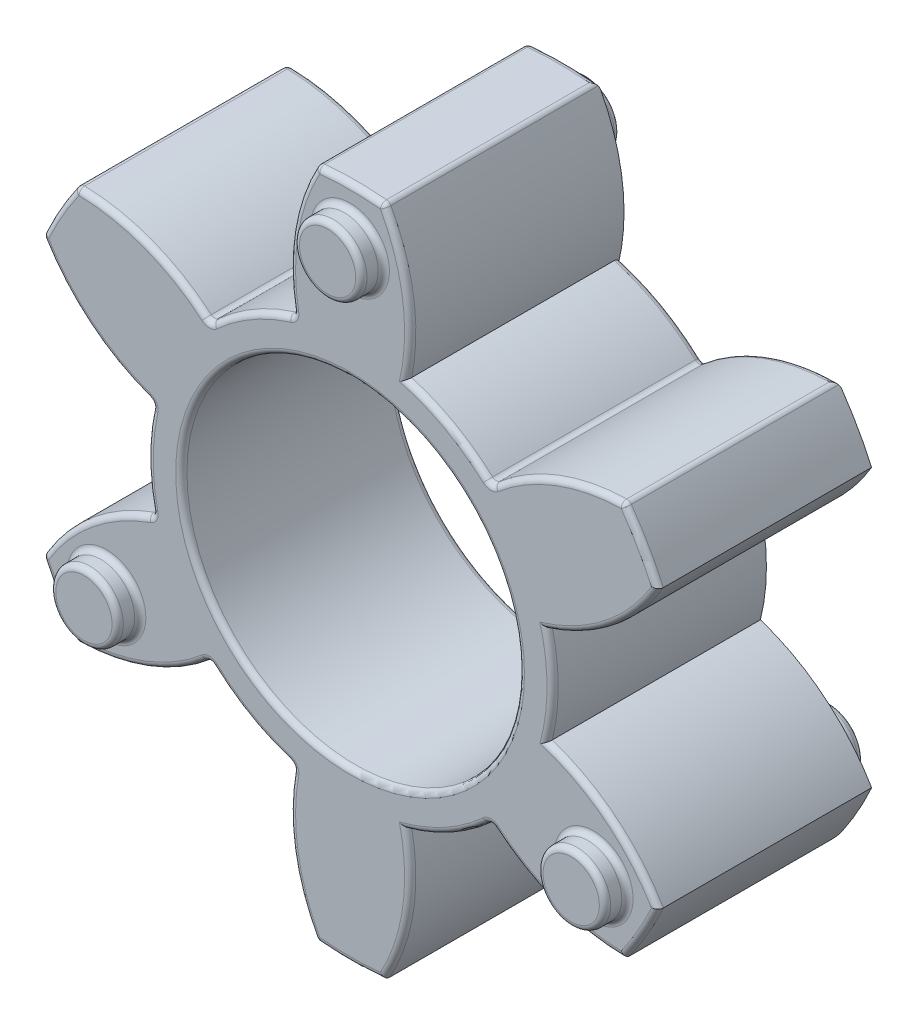
SolidWorks part; units mm, degrees
ref_plane "Front Plane" through (0, 0, 0) normal (0, 0, 1) x (1, 0, 0)
ref_plane "Top Plane" through (0, 0, 0) normal (0, 1, 0) x (1, 0, 0)
ref_plane "Right Plane" through (0, 0, 0) normal (1, 0, 0) x (0, 0, -1)
sketch "Sketch1" plane through (0, 0, 0) normal (0, 0, 1) x (1, 0, 0)
  line L0 (0, 0) -> (0, 50000) construction
  line L1 (0, 0) -> (-50000, 0) construction
  circle A0 centre (0, 0) radius 7.5
  circle A1 centre (0, 0) radius 12.5 construction
  arc A2 (-8.7337, 2.173) -> (-8.7337, -2.173) centre (0, 0) ccw
  circle A3 centre (0, 12.5) radius 1.5
  arc A4 (-12.1753, 8.7614) -> (-13.6753, 6.1634) centre (0, 0) ccw
  arc A5 (-2.485, 8.6501) -> (-1.5, 14.9248) centre (6.3267, 10.4815) cw
  arc A6 (2.485, 8.6501) -> (1.5, 14.9248) centre (-6.3267, 10.4815) ccw
  arc A7 (6.2487, 6.4771) -> (12.1753, 8.7614) centre (12.2406, -0.2383) cw
  arc A8 (8.7337, 2.173) -> (13.6753, 6.1634) centre (5.9139, 10.7198) ccw
  arc A10 (8.7337, -2.173) -> (13.6753, -6.1634) centre (5.9139, -10.7198) cw
  arc A11 (6.2487, -6.4771) -> (12.1753, -8.7614) centre (12.2406, 0.2383) ccw
  circle A12 centre (10.8253, -6.25) radius 1.5
  arc A13 (2.485, -8.6501) -> (1.5, -14.9248) centre (-6.3267, -10.4815) cw
  arc A14 (-2.485, -8.6501) -> (-1.5, -14.9248) centre (6.3267, -10.4815) ccw
  arc A16 (-6.2487, -6.4771) -> (-12.1753, -8.7614) centre (-12.2406, 0.2383) cw
  arc A17 (-8.7337, -2.173) -> (-13.6753, -6.1634) centre (-5.9139, -10.7198) ccw
  circle A18 centre (-10.8253, -6.25) radius 1.5
  arc A19 (-8.7337, 2.173) -> (-13.6753, 6.1634) centre (-5.9139, 10.7198) cw
  arc A20 (-6.2487, 6.4771) -> (-12.1753, 8.7614) centre (-12.2406, -0.2383) ccw
  arc A22 (-2.485, 8.6501) -> (-6.2487, 6.4771) centre (0, 0) ccw
  arc A23 (6.2487, 6.4771) -> (2.485, 8.6501) centre (0, 0) ccw
  arc A24 (8.7337, -2.173) -> (8.7337, 2.173) centre (0, 0) ccw
  arc A25 (2.485, -8.6501) -> (6.2487, -6.4771) centre (0, 0) ccw
  arc A26 (-6.2487, -6.4771) -> (-2.485, -8.6501) centre (0, 0) ccw
  arc A27 (1.5, 14.9248) -> (-1.5, 14.9248) centre (0, 0) ccw
  arc A28 (13.6753, 6.1634) -> (12.1753, 8.7614) centre (0, 0) ccw
  arc A29 (12.1753, -8.7614) -> (13.6753, -6.1634) centre (0, 0) ccw
  arc A30 (-1.5, -14.9248) -> (1.5, -14.9248) centre (0, 0) ccw
  arc A31 (-13.6753, -6.1634) -> (-12.1753, -8.7614) centre (0, 0) ccw
  circle A32 centre (-10.8253, 6.25) radius 1.5 [skipped]
  circle A33 centre (10.8253, 6.25) radius 1.5 [skipped]
  circle A34 centre (0, -12.5) radius 1.5 [skipped]
  point P61 (0, 0)
  dimension "D1" = 15
  dimension "D2" = 18
  dimension "D3" = 25
  dimension "D4" = 3
  dimension "D5" = 30
  dimension "D6" = 9
  dimension "D7" = 4.97
  dimension "D8" = 3
  dimension "D9" = 6
extrude "Boss-Extrude2" add sketch "Sketch1" along normal mid plane 9.5
extrude "Boss-Extrude3" add sketch "Sketch1<2>" along normal mid plane 11.5 contours A3 region at (0, 12.5, 0)
sketch "Sketch1<2>" plane through (0, 0, 0) normal (0, 0, 1) x (1, 0, 0) same geometry as "Sketch1"
extrude "Boss-Extrude4" add sketch "Sketch1<3>" along normal mid plane 11.5 contours A12 | A18 region at (10.8253, -6.25, 0) region at (-10.8253, -6.25, 0)
sketch "Sketch1<3>" plane through (0, 0, 0) normal (0, 0, 1) x (1, 0, 0) same geometry as "Sketch1"
fillet "Fillet1" radius 0.25 70 edges at (-9.0038, -8.1595, -4.75) (4.5, -7.7942, -4.75) (4.5, 7.7942, -4.75) (-9.3253, -6.25, -5.75) (-9.3253, -6.25, 5.75) (-9.3253, -6.25, -4.75) (12.3253, -6.25, -5.75) (12.3253, -6.25, 5.75) (12.3253, -6.25, -4.75) (1.5, 12.5, -5.75) (1.5, 12.5, 5.75) (1.5, 12.5, -4.75) (-9.3253, -6.25, 4.75) (12.3253, -6.25, 4.75) (1.5, 12.5, 4.75) (7.5, 0, -4.75) (7.5, 0, 4.75) (-4.5, 7.7942, -4.75) (-9.0038, 8.1595, -4.75) (-12.9904, 7.5, -4.75) (-11.5682, 3.7178, -4.75) (-9, 0, -4.75) (-11.5682, -3.7178, -4.75) (-12.9904, -7.5, -4.75) (-4.5, -7.7942, -4.75) (-2.5644, -11.8773, -4.75) (9.0038, -8.1595, -4.75) (9.0038, 8.1595, -4.75) (0, 15, -4.75) (-2.5644, 11.8773, -4.75) (-4.5, 7.7942, 4.75) (-9.0038, 8.1595, 4.75) (-12.9904, 7.5, 4.75) (-11.5682, 3.7178, 4.75) (-9, 0, 4.75) (-11.5682, -3.7178, 4.75) (-12.9904, -7.5, 4.75) (-9.0038, -8.1595, 4.75) (-4.5, -7.7942, 4.75) (-2.5644, -11.8773, 4.75) (0, -15, 4.75) (2.5644, -11.8773, 4.75) (4.5, -7.7942, 4.75) (9.0038, -8.1595, 4.75) (12.9904, -7.5, 4.75) (11.5682, -3.7178, 4.75) (9, 0, 4.75) (11.5682, 3.7178, 4.75) (12.9904, 7.5, 4.75) (9.0038, 8.1595, 4.75) (4.5, 7.7942, 4.75) (2.5644, 11.8773, 4.75) (0, 15, 4.75) (-2.5644, 11.8773, 4.75) (-2.485, 8.6501, 0) (-1.5, 14.9248, 0) (1.5, 14.9248, 0) (6.2487, 6.4771, 0) (12.1753, 8.7614, 0) (6.2487, -6.4771, 0) (-1.5, -14.9248, 0) (-2.485, -8.6501, 0) (-6.2487, -6.4771, 0) (-12.1753, -8.7614, 0) (-13.6753, -6.1634, 0) (-8.7337, -2.173, 0) (-8.7337, 2.173, 0) (-13.6753, 6.1634, 0) (-12.1753, 8.7614, 0) (-6.2487, 6.4771, 0)
